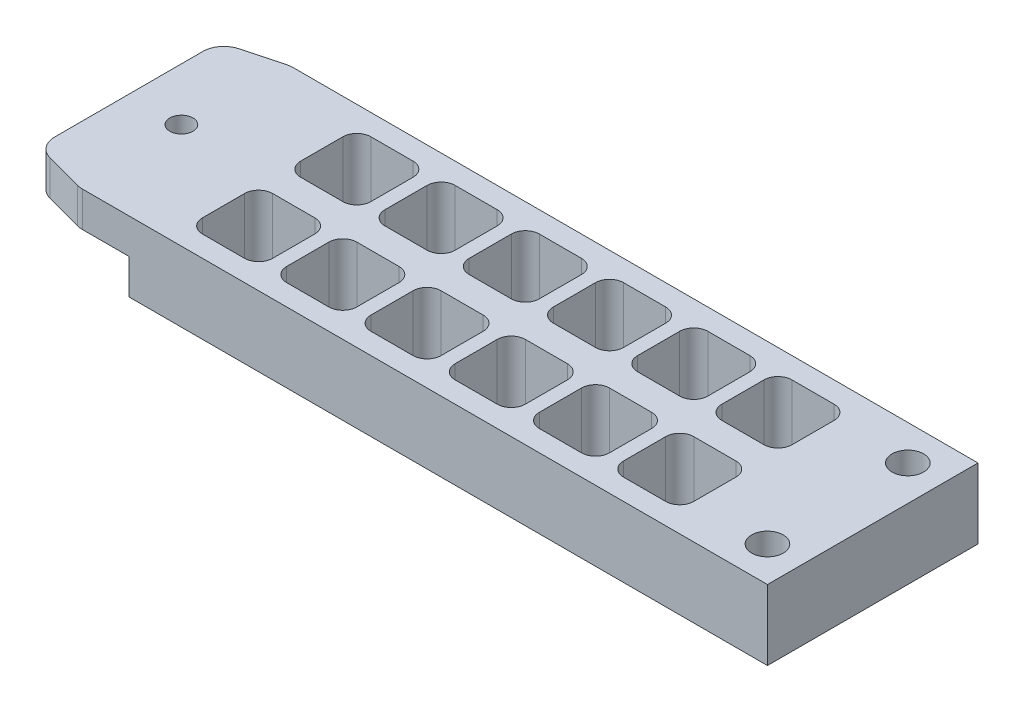
SolidWorks part; units mm, degrees
material "3.1355 (EN-AW 2024)"
ref_plane "Front" through (0, 0, 0) normal (0, 0, 1) x (1, 0, 0)
ref_plane "Top" through (0, 0, 0) normal (0, 1, 0) x (1, 0, 0)
ref_plane "Right" through (0, 0, 0) normal (1, 0, 0) x (0, 0, -1)
sketch "Эскиз1" plane through (0, 0, 0) normal (0, 1, 0) x (1, 0, 0)
  line L0 (106, 15) -> (15, 15) construction
  line L1 (15, 0) -> (106, 0)
  line L2 (0, 0) -> (0, 30) construction
  line L3 (15, 30) -> (106, 30)
  line L4 (106, 0) -> (106, 30)
  line L5 (0, 0) -> (15, 0) construction
  line L6 (0, 2.1436) -> (0, 27.8564)
  line L7 (15, 30) -> (8, 30)
  line L8 (8, 30) -> (0, 27.8564)
  line L9 (8, 0) -> (0, 2.1436)
  line L10 (15, 0) -> (8, 0)
  arc A0 (15, 30) -> (15, 0) centre (15, 15) ccw construction
  point P13 (0, 15)
  dimension "D1" = 30
  dimension "D2" = 106
  dimension "D4" = 7
  dimension "D5" = 75
extrude "Бобышка-Вытянуть1" add sketch "Эскиз1" along normal blind 10
sketch "Эскиз4" plane through (0, 0, 0) normal (0, -1, 0) x (1, 0, 0)
  line L0 (8, 0) -> (106, 0) construction
  line L1 (0, -30) -> (15, -30)
  line L2 (0, -30) -> (0, 0)
  line L3 (0, 0) -> (15, 0)
  line L4 (15, -30) -> (15, 0)
  line L5 (0, -27.8564) -> (0, -2.1436) construction
  line L6 (106, -30) -> (8, -30) construction
  dimension "D1" = 15
extrude "Вырез-Вытянуть2" cut sketch "Эскиз4" against normal blind 5
fillet "Скругление1" radius 3 4 edges at (8, 7.5, -30) (0, 7.5, -27.8564) (0, 7.5, -2.1436) (8, 7.5, 0)
sketch "Эскиз5" plane through (0, 0, 0) normal (0, -1, 0) x (1, 0, 0)
  line L0 (106, -15) -> (96, -15) construction
  line L1 (106, 0) -> (106, -30) construction
  line L2 (15, -15) -> (20.5, -15) construction
  line L3 (15, -30) -> (15, 0) construction
  line L4 (106, -30) -> (15, -30) construction
  line L5 (22.5, -17) -> (28.5, -17)
  line L6 (20.5, -19) -> (20.5, -25)
  line L7 (22.5, -27) -> (28.5, -27)
  line L8 (30.5, -19) -> (30.5, -25)
  line L9 (20.5, -17) -> (30.5, -27) construction
  line L10 (20.5, -27) -> (30.5, -17) construction
  line L11 (34.5, -17) -> (40.5, -17)
  line L12 (32.5, -19) -> (32.5, -25)
  line L13 (34.5, -27) -> (40.5, -27)
  line L14 (42.5, -19) -> (42.5, -25)
  line L15 (32.5, -17) -> (42.5, -27) construction
  line L16 (32.5, -27) -> (42.5, -17) construction
  line L17 (46.5, -17) -> (52.5, -17)
  line L18 (44.5, -19) -> (44.5, -25)
  line L19 (46.5, -27) -> (52.5, -27)
  line L20 (54.5, -19) -> (54.5, -25)
  line L21 (44.5, -17) -> (54.5, -27) construction
  line L22 (44.5, -27) -> (54.5, -17) construction
  line L23 (58.5, -17) -> (64.5, -17)
  line L24 (56.5, -19) -> (56.5, -25)
  line L25 (58.5, -27) -> (64.5, -27)
  line L26 (66.5, -19) -> (66.5, -25)
  line L27 (56.5, -17) -> (66.5, -27) construction
  line L28 (56.5, -27) -> (66.5, -17) construction
  line L29 (70.5, -17) -> (76.5, -17)
  line L30 (68.5, -19) -> (68.5, -25)
  line L31 (70.5, -27) -> (76.5, -27)
  line L32 (78.5, -19) -> (78.5, -25)
  line L33 (68.5, -17) -> (78.5, -27) construction
  line L34 (68.5, -27) -> (78.5, -17) construction
  line L35 (82.5, -17) -> (88.5, -17)
  line L36 (80.5, -19) -> (80.5, -25)
  line L37 (82.5, -27) -> (88.5, -27)
  line L38 (90.5, -19) -> (90.5, -25)
  line L39 (80.5, -17) -> (90.5, -27) construction
  line L40 (80.5, -27) -> (90.5, -17) construction
  line L41 (25.5, -22) -> (37.5, -22) construction
  line L42 (25.5, -8) -> (37.5, -8) construction
  line L43 (80.5, -3) -> (90.5, -13) construction
  line L44 (80.5, -13) -> (90.5, -3) construction
  line L45 (68.5, -3) -> (78.5, -13) construction
  line L46 (68.5, -13) -> (78.5, -3) construction
  line L47 (56.5, -3) -> (66.5, -13) construction
  line L48 (56.5, -13) -> (66.5, -3) construction
  line L49 (44.5, -3) -> (54.5, -13) construction
  line L50 (44.5, -13) -> (54.5, -3) construction
  line L51 (32.5, -3) -> (42.5, -13) construction
  line L52 (32.5, -13) -> (42.5, -3) construction
  line L53 (20.5, -3) -> (30.5, -13) construction
  line L54 (20.5, -13) -> (30.5, -3) construction
  line L55 (90.5, -11) -> (90.5, -5)
  line L56 (82.5, -3) -> (88.5, -3)
  line L57 (80.5, -11) -> (80.5, -5)
  line L58 (82.5, -13) -> (88.5, -13)
  line L59 (78.5, -11) -> (78.5, -5)
  line L60 (70.5, -3) -> (76.5, -3)
  line L61 (68.5, -11) -> (68.5, -5)
  line L62 (70.5, -13) -> (76.5, -13)
  line L63 (66.5, -11) -> (66.5, -5)
  line L64 (58.5, -3) -> (64.5, -3)
  line L65 (56.5, -11) -> (56.5, -5)
  line L66 (58.5, -13) -> (64.5, -13)
  line L67 (54.5, -11) -> (54.5, -5)
  line L68 (46.5, -3) -> (52.5, -3)
  line L69 (44.5, -11) -> (44.5, -5)
  line L70 (46.5, -13) -> (52.5, -13)
  line L71 (42.5, -11) -> (42.5, -5)
  line L72 (34.5, -3) -> (40.5, -3)
  line L73 (32.5, -11) -> (32.5, -5)
  line L74 (34.5, -13) -> (40.5, -13)
  line L75 (30.5, -11) -> (30.5, -5)
  line L76 (22.5, -3) -> (28.5, -3)
  line L77 (20.5, -11) -> (20.5, -5)
  line L78 (22.5, -13) -> (28.5, -13)
  arc A0 (28.5, -27) -> (30.5, -25) centre (28.5, -25) ccw
  arc A1 (22.5, -27) -> (20.5, -25) centre (22.5, -25) cw
  arc A2 (20.5, -19) -> (22.5, -17) centre (22.5, -19) cw
  arc A3 (28.5, -17) -> (30.5, -19) centre (28.5, -19) cw
  arc A4 (40.5, -27) -> (42.5, -25) centre (40.5, -25) ccw
  arc A5 (34.5, -27) -> (32.5, -25) centre (34.5, -25) cw
  arc A6 (32.5, -19) -> (34.5, -17) centre (34.5, -19) cw
  arc A7 (40.5, -17) -> (42.5, -19) centre (40.5, -19) cw
  arc A8 (52.5, -27) -> (54.5, -25) centre (52.5, -25) ccw
  arc A9 (46.5, -27) -> (44.5, -25) centre (46.5, -25) cw
  arc A10 (44.5, -19) -> (46.5, -17) centre (46.5, -19) cw
  arc A11 (52.5, -17) -> (54.5, -19) centre (52.5, -19) cw
  arc A12 (64.5, -27) -> (66.5, -25) centre (64.5, -25) ccw
  arc A13 (58.5, -27) -> (56.5, -25) centre (58.5, -25) cw
  arc A14 (56.5, -19) -> (58.5, -17) centre (58.5, -19) cw
  arc A15 (64.5, -17) -> (66.5, -19) centre (64.5, -19) cw
  arc A16 (76.5, -27) -> (78.5, -25) centre (76.5, -25) ccw
  arc A17 (70.5, -27) -> (68.5, -25) centre (70.5, -25) cw
  arc A18 (68.5, -19) -> (70.5, -17) centre (70.5, -19) cw
  arc A19 (76.5, -17) -> (78.5, -19) centre (76.5, -19) cw
  arc A20 (88.5, -27) -> (90.5, -25) centre (88.5, -25) ccw
  arc A21 (82.5, -27) -> (80.5, -25) centre (82.5, -25) cw
  arc A22 (80.5, -19) -> (82.5, -17) centre (82.5, -19) cw
  arc A23 (88.5, -17) -> (90.5, -19) centre (88.5, -19) cw
  arc A24 (88.5, -13) -> (90.5, -11) centre (88.5, -11) ccw
  arc A25 (80.5, -11) -> (82.5, -13) centre (82.5, -11) ccw
  arc A26 (82.5, -3) -> (80.5, -5) centre (82.5, -5) ccw
  arc A27 (88.5, -3) -> (90.5, -5) centre (88.5, -5) cw
  arc A28 (76.5, -13) -> (78.5, -11) centre (76.5, -11) ccw
  arc A29 (68.5, -11) -> (70.5, -13) centre (70.5, -11) ccw
  arc A30 (70.5, -3) -> (68.5, -5) centre (70.5, -5) ccw
  arc A31 (76.5, -3) -> (78.5, -5) centre (76.5, -5) cw
  arc A32 (64.5, -13) -> (66.5, -11) centre (64.5, -11) ccw
  arc A33 (56.5, -11) -> (58.5, -13) centre (58.5, -11) ccw
  arc A34 (58.5, -3) -> (56.5, -5) centre (58.5, -5) ccw
  arc A35 (64.5, -3) -> (66.5, -5) centre (64.5, -5) cw
  arc A36 (52.5, -13) -> (54.5, -11) centre (52.5, -11) ccw
  arc A37 (44.5, -11) -> (46.5, -13) centre (46.5, -11) ccw
  arc A38 (46.5, -3) -> (44.5, -5) centre (46.5, -5) ccw
  arc A39 (52.5, -3) -> (54.5, -5) centre (52.5, -5) cw
  arc A40 (40.5, -13) -> (42.5, -11) centre (40.5, -11) ccw
  arc A41 (32.5, -11) -> (34.5, -13) centre (34.5, -11) ccw
  arc A42 (34.5, -3) -> (32.5, -5) centre (34.5, -5) ccw
  arc A43 (40.5, -3) -> (42.5, -5) centre (40.5, -5) cw
  arc A44 (28.5, -13) -> (30.5, -11) centre (28.5, -11) ccw
  arc A45 (20.5, -11) -> (22.5, -13) centre (22.5, -11) ccw
  arc A46 (22.5, -3) -> (20.5, -5) centre (22.5, -5) ccw
  arc A47 (28.5, -3) -> (30.5, -5) centre (28.5, -5) cw
  point P8 (25.5, -22)
  point P28 (37.5, -22)
  point P45 (49.5, -22)
  point P62 (61.5, -22)
  point P79 (73.5, -22)
  point P96 (85.5, -22)
  point P212 (85.5, -8)
  point P213 (73.5, -8)
  point P214 (61.5, -8)
  point P215 (49.5, -8)
  dimension "D5" = 2
  dimension "D1" = 10
  dimension "D2" = 5.5
  dimension "D3" = 10
  dimension "D4" = 3
  dimension "D7" = 12
  dimension "D6" = 6
extrude "Вырез-Вытянуть3" cut sketch "Эскиз5" against normal through all
sketch "Эскиз6" plane through (0, 10, 0) normal (0, 1, 0) x (1, 0, 0)
  line L0 (101, 30) -> (101, 0) construction
  line L1 (106, 30) -> (8.395, 30) construction
  line L2 (8.395, 0) -> (106, 0) construction
  line L3 (106, 0) -> (106, 30) construction
  point P8 (101, 25)
  point P9 (101, 5)
  dimension "D1" = 5
  dimension "D2" = 5
  dimension "D3" = 5
hole_wizard "Отверстие с зазором M41" positions "Эскиз8" profile "Эскиз7" hole size "M4" standard "Ansi Metric" end condition through all
sketch "Эскиз8" plane through (0, 10, 0) normal (0, 1, 0) x (1, 0, 0)
  point P0 (101, 25)
  point P3 (101, 5)
sketch "Эскиз7" plane through (101, 10, -25) normal (1, 0, 0) x (0, 0, 1)
  line L0 (0, 0) -> (0, 10)
  line L1 (0, 10) -> (2.25, 10)
  line L2 (2.25, 10) -> (2.25, 0)
  line L5 (2.25, 0) -> (0, 0)
  line L11 (0, -6.35) -> (0, 107.95) construction
  dimension "Диаметр сквозного отверстия" = 4.5
  dimension "Глубина сквозного отверстия" = 10
sketch "Эскиз10" plane through (0, 5, 0) normal (0, -1, 0) x (1, 0, 0)
  line L0 (0, -15) -> (7.5, -15) construction
  line L1 (0, -4.4456) -> (0, -25.5544) construction
  dimension "D1" = 7.5
hole_wizard "Отверстие обработанное метчиком M4x0.71" positions "Эскиз12" profile "Эскиз11" tap size "M4x0.7" standard "Ansi Metric" end condition through all
sketch "Эскиз12" plane through (0, 5, 0) normal (0, -1, 0) x (-1, 0, 0)
  point P0 (-7.5, 15)
sketch "Эскиз11" plane through (7.5, 5, -15) normal (1, 0, 0) x (0, 0, -1)
  line L0 (0, 0) -> (0, 5)
  line L1 (0, 5) -> (1.65, 5)
  line L2 (1.65, 5) -> (1.65, 0)
  line L5 (1.65, 0) -> (0, 0)
  line L11 (0, -6.35) -> (0, 107.95) construction
  dimension "Диаметр проходного сверла" = 3.3
  dimension "Глубина проходного сверла" = 5
cosmetic thread "Отверстие резьбы1" parameters "D2"=4
